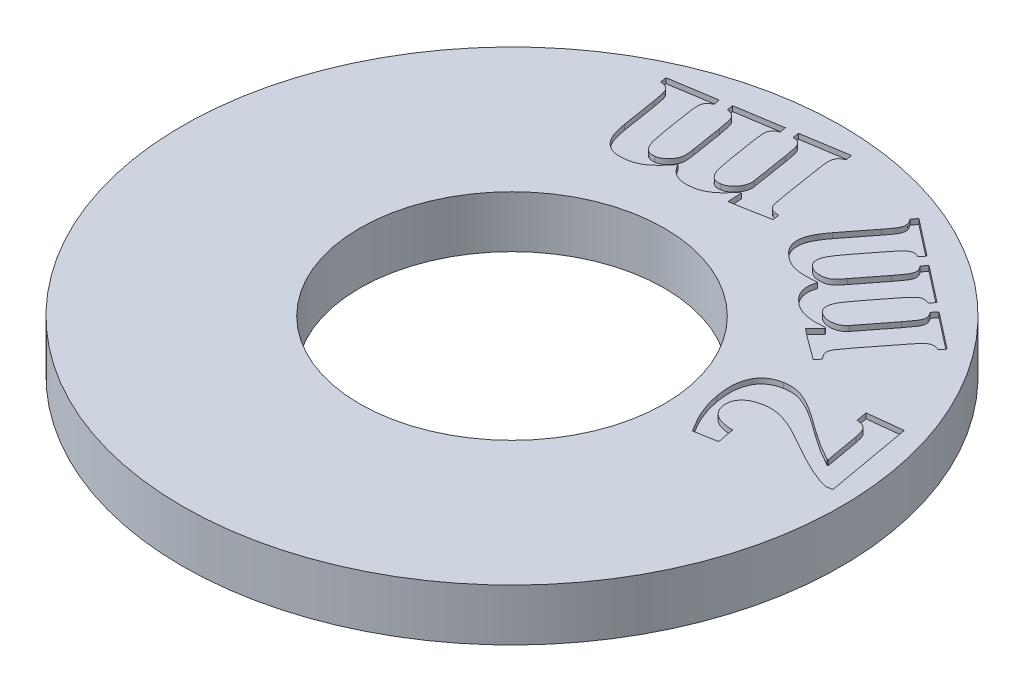
SolidWorks part; units mm, degrees
ref_plane "Front Plane" through (0, 0, 0) normal (0, 0, 1) x (1, 0, 0)
ref_plane "Top Plane" through (0, 0, 0) normal (0, 1, 0) x (1, 0, 0)
ref_plane "Right Plane" through (0, 0, 0) normal (1, 0, 0) x (0, 0, -1)
sketch "Sketch1" plane through (0, 0, 0) normal (0, 1, 0) x (1, 0, 0)
  circle A0 centre (0, 0) radius 12.7
  dimension "D1" = 25.4
extrude "Boss-Extrude1" add sketch "Sketch1" along normal blind 2
sketch "Sketch2" plane through (0, 0, 0) normal (0, -1, 0) x (-1, 0, 0)
  circle A0 centre (0, 0) radius 5.8674
  dimension "D1" = 11.7348
extrude "Cut-Extrude1" cut sketch "Sketch2" against normal through all
sketch "Sketch4" plane through (0, 2, 0) normal (0, 1, 0) x (1, 0, 0)
  circle A0 centre (0, 0) radius 12.0429 construction
  text T0 "<b>2mm</b>" font "Cambria" height 5.08
extrude "Cut-Extrude2" cut sketch "Sketch4" against normal blind 0.2
